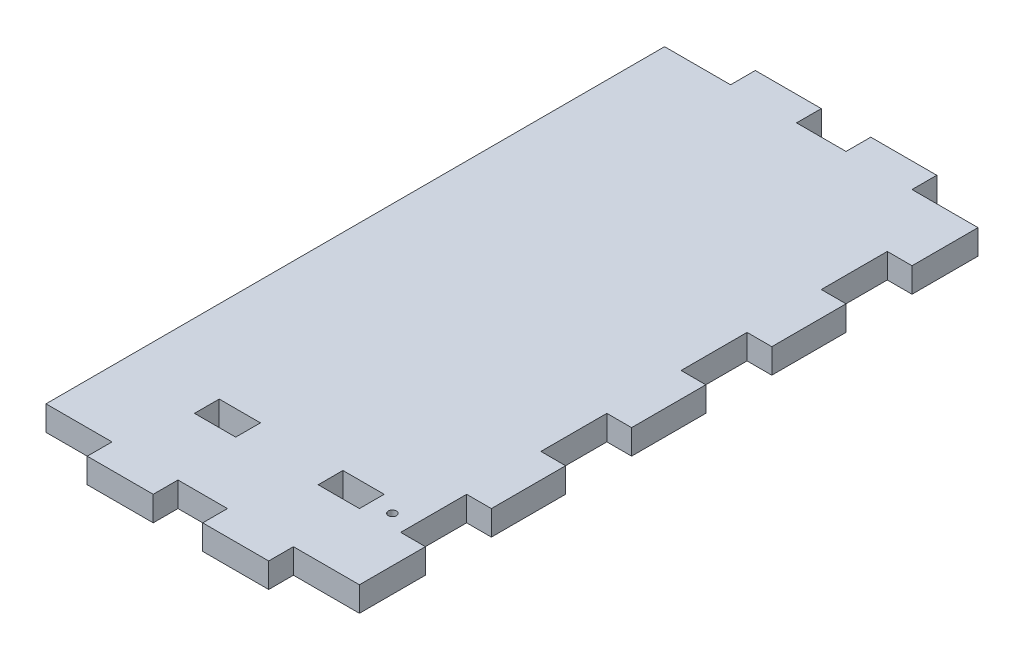
SolidWorks part; units mm, degrees
ref_plane "Front Plane" through (0, 0, 0) normal (0, 0, 1) x (1, 0, 0)
ref_plane "Top Plane" through (0, 0, 0) normal (0, 1, 0) x (1, 0, 0)
ref_plane "Right Plane" through (0, 0, 0) normal (1, 0, 0) x (0, 0, -1)
sketch "Sketch1" plane through (0, 0, 0) normal (0, 1, 0) x (1, 0, 0)
  line L0 (-25, 81) -> (-25, -81)
  line L1 (-35, 81) -> (35, 81)
  line L2 (-35, 81) -> (-35, -81)
  line L3 (-35, -81) -> (35, -81)
  line L4 (35, 81) -> (35, -81)
  line L5 (-35, 81) -> (35, -81) construction
  line L6 (-35, -81) -> (35, 81) construction
  point P0 (0, 0)
  dimension "D1" = 70
  dimension "D3" = 10
  dimension "D2" = 162
sketch "Sketch2" plane through (0, 0, 0) normal (0, 0, 1) x (1, 0, 0)
  line L0 (0, 0) -> (0, 6) construction
  line L1 (-35, 0) -> (35, 0) construction
  dimension "D1" = 6
extrude "Boss-Extrude1" add sketch "Sketch1" along normal up to vertex (6 mm away) contours L4 L1 L0 L3 | L2 L3 L0 L1 region at (5, 0, 0) region at (-30, 0, 0) up to point (0, 6, 0)
sketch "Sketch4" plane through (0, 6, 0) normal (0, 1, 0) x (1, 0, 0)
  line L0 (35, 81) -> (35, -81) construction
  line L1 (35, 81) -> (35, -81)
  line L2 (35, 81) -> (41, 81)
  line L3 (41, 81) -> (41, -81)
  line L4 (41, -81) -> (35, -81)
  point P2 (35, -81.8412)
  dimension "D1" = 6
extrude "Boss-Extrude2" add sketch "Sketch4" against normal up to surface (6 mm away) up to face at (0, 0, 0)
sketch "Sketch5" plane through (0, 6, 0) normal (0, 1, 0) x (1, 0, 0)
  line L0 (-35, -75) -> (35, -75) construction
  line L2 (-35, 81) -> (-35, -81) construction
  line L3 (35, -75) -> (35, 0) construction
  line L5 (35, 0) -> (41, 0) construction
  line L6 (41, -81) -> (41, 81) construction
  line L7 (-35, -75) -> (-35, -81) construction
  line L8 (38, -43) -> (38, -25) construction
  line L9 (35, -59) -> (41, -59)
  line L10 (35, -59) -> (35, -43)
  line L11 (35, -43) -> (41, -43)
  line L12 (41, -59) -> (41, -43)
  line L13 (35, -9) -> (41, -9)
  line L14 (35, -9) -> (35, -25)
  line L15 (35, -25) -> (41, -25)
  line L16 (41, -9) -> (41, -25)
  line L17 (38, -9) -> (38, 9)
  line L18 (-35, -81) -> (41, -81) construction
  line L19 (41, -81) -> (25, -81)
  line L20 (41, -81) -> (41, -75)
  line L21 (41, -75) -> (25, -75)
  line L22 (25, -81) -> (25, -75)
  line L23 (-35, -75) -> (-19, -75)
  line L24 (-35, -75) -> (-35, -81)
  line L25 (-35, -81) -> (-19, -81)
  line L26 (-19, -75) -> (-19, -81)
  line L28 (-19, -81) -> (-3, -81)
  line L29 (-19, -81) -> (-19, -75)
  line L30 (-19, -75) -> (-3, -75)
  line L31 (-3, -81) -> (-3, -75)
  line L32 (25, -75) -> (9, -75)
  line L33 (25, -75) -> (25, -81)
  line L34 (25, -81) -> (9, -81)
  line L35 (9, -75) -> (9, -81)
  line L36 (-3, -75) -> (9, -75)
  line L37 (-3, -75) -> (-3, -81)
  line L38 (-3, -81) -> (9, -81)
  line L39 (9, -75) -> (9, -81)
  point P23 (38, 0)
  point P37 (35, -62.2019)
  point P38 (35, -48.8329)
  line M10 (-35, -81) -> (41, -81)
  line M11 (41, -81) -> (41, 81)
  line M13 (-35, 81) -> (-35, -81)
  dimension "D1" = 6
  dimension "D3" = 16
extrude "Cut-Extrude1" cut sketch "Sketch5" against normal through all contours L11 L10 L9 M11 | L14 L15 L13 M11 | L22 L21 M10 M11 | L26 L23 M13 M10 | L36 L31 L35 M10 region at (38, 6, 51) region at (38, 6, 17) region at (33, 6, 78) region at (3, 6, 78) region at (-27, 6, 78)
mirror "Mirror1" about plane through (0, 0, 0) normal (0, 0, 1) of "Cut-Extrude1"
sketch "Sketch6" plane through (0, 6, 0) normal (0, 1, 0) x (1, 0, 0)
  line L0 (25, -56) -> (35, -56) construction
  line L1 (25, -59) -> (15, -59)
  line L2 (25, -59) -> (25, -53)
  line L3 (25, -53) -> (15, -53)
  line L4 (15, -59) -> (15, -53)
  line L5 (-5, -59) -> (-15, -59)
  line L6 (-5, -59) -> (-5, -53)
  line L7 (-5, -53) -> (-15, -53)
  line L8 (-15, -59) -> (-15, -53)
  line L9 (35, -59) -> (35, -43) construction
  circle A0 centre (30, -56) radius 1
  dimension "D1" = 2
extrude "Cut-Extrude2" cut sketch "Sketch6" against normal through all
equation "\"glass_width\" = 150"
equation "\"glass_height\"= 100"
equation "\"glass_thickness\"= 4"
equation "\"brood_space\"= 42"
equation "\"t1\"= 6"
equation "\"t2\"= 3.2"
equation "\"box_depth\"= \"brood_space\" + \"glass_thickness\" + \"glass_thickness\" + \"t2\" + \"t2\""
equation "\"box_width\"= \"glass_width\" + \"t1\" + \"t1\""
equation "\"food_height\"= 70"
equation "\"box_height\" = \"glass_height\" + ( \"t1\" * 3 ) + \"food_height\""
equation "\"D1@Sketch2\"=\"t1\""
equation "\"D1@Sketch1\"=\"food_height\""
equation "\"D2@Sketch1\"=\"box_width\""
equation "\"D1@Sketch4\"=\"t1\""
equation "\"D1@Sketch5\"=\"t1\""
